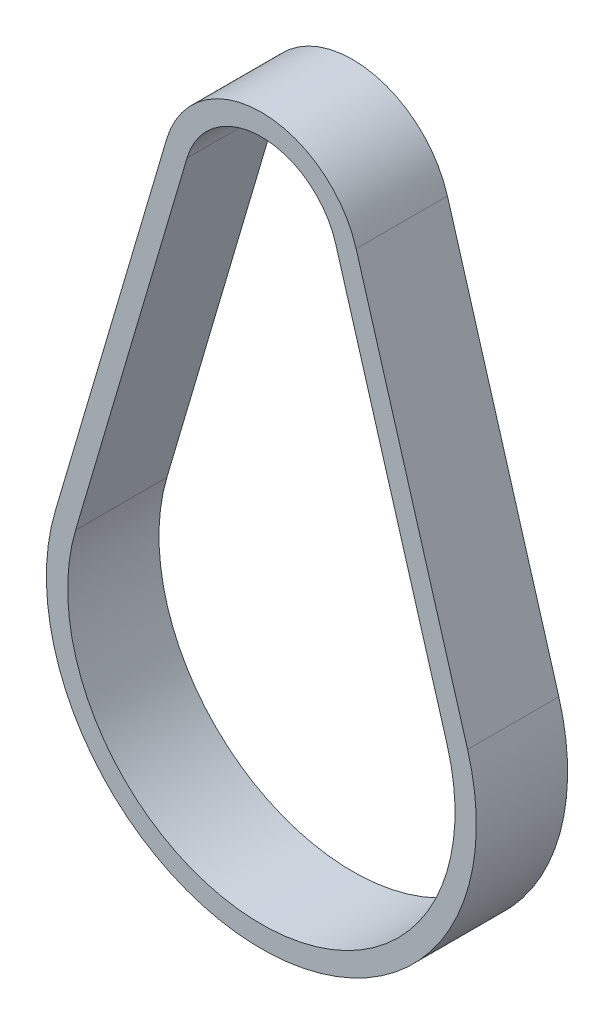
SolidWorks part; units mm, degrees
ref_plane "Front Plane" through (0, 0, 0) normal (0, 0, 1) x (1, 0, 0)
ref_plane "Top Plane" through (0, 0, 0) normal (0, 1, 0) x (1, 0, 0)
ref_plane "Right Plane" through (0, 0, 0) normal (1, 0, 0) x (0, 0, -1)
sketch "Sketch2" plane through (0, 0, 0) normal (0, 0, 1) x (1, 0, 0)
  line L0 (0, 0) -> (1, 0) construction
  line L1 (0, 0) -> (0, 1) construction
  line L2 (-24.6186, -2.3247) -> (-17.2953, 22.5163)
  line L3 (-7.5212, 22.5163) -> (-0.1978, -2.3247)
  arc A0 (-0.1978, -2.3247) -> (-24.6186, -2.3247) centre (-12.4082, -5.9244) cw
  arc A1 (-17.2953, 22.5163) -> (-7.5212, 22.5163) centre (-12.4082, 21.0756) cw
extrude "Extrude-Thin1" add sketch "Sketch2" against normal blind 6 thin thin type one direction wall 1.4
